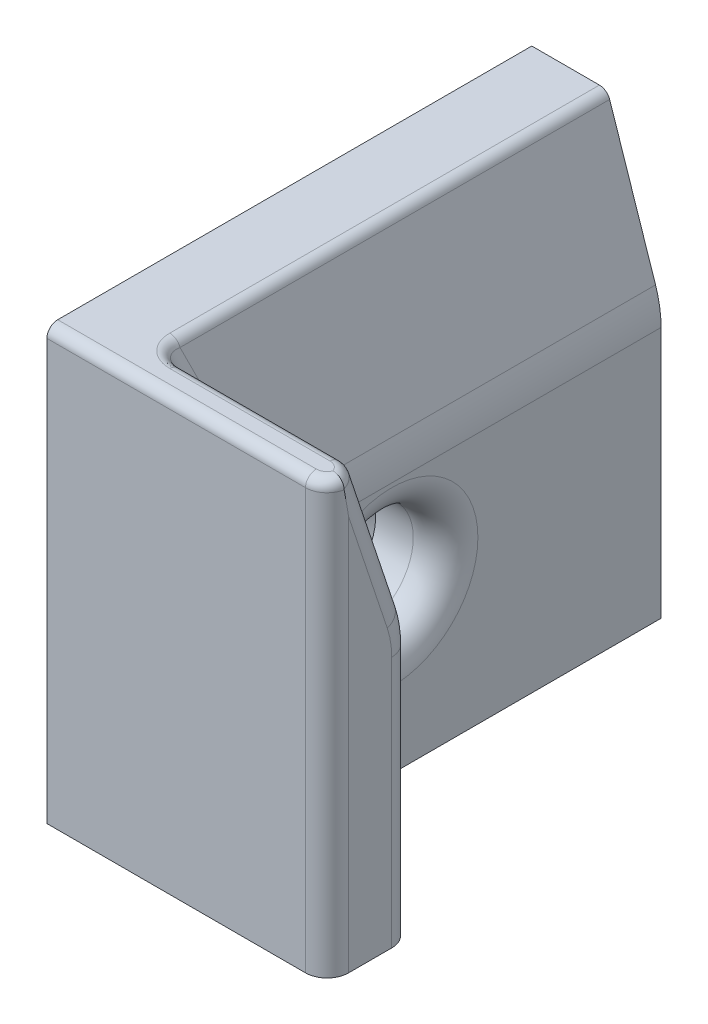
SolidWorks part; units mm, degrees
material "ABS"
ref_plane "Front" through (0, 0, 0) normal (0, 0, 1) x (1, 0, 0)
ref_plane "Top" through (0, 0, 0) normal (0, 1, 0) x (1, 0, 0)
ref_plane "Right" through (0, 0, 0) normal (1, 0, 0) x (0, 0, -1)
sketch "Esquisse1" plane through (0, 0, 0) normal (0, 1, 0) x (1, 0, 0)
  line L0 (-6, 0) -> (6, 0)
  line L1 (6, 0) -> (6, -37)
  line L2 (6, -37) -> (20, -37)
  line L3 (20, -37) -> (20, -45)
  line L4 (20, -45) -> (-6, -45)
  line L7 (-6, -45) -> (-6, 0)
  dimension "D2" = 12
  dimension "D4" = 8
  dimension "D5" = 37
  dimension "D6" = 14
extrude "Boss.-Extru.1" add sketch "Esquisse1" along normal blind 25 and the other way blind 15 from offset 0
chamfer "Chanfrein1" distance 15 distance2 5 2 edges at (13, 25, 37) (6, 25, 18.5) first distance on face at (13, 5, 37) first distance on face at (6, 5, 18.5)
fillet "Congé1" radius 10 2 edges at (13, 10, 37) (6, 10, 18.5)
fillet "Congé2" radius 2 7 edges at (3.2434, 18.2698, 39.7566) (5.8709, 9.979, 37.1291) (20, 18.2698, 39.7566) (20, 9.979, 37.1291) (20, 5, 45) (6, -3.3114, 37) (20, -3.3114, 37)
fillet "Congé3" radius 1 6 edges at (6, 25, 45) (19.2085, 25, 44.5936) (19.2085, 25, 42.4284) (10.4487, 25, 42) (1.5447, 25, 41.4553) (1, 25, 20.0513)
sketch "Esquisse2" plane through (0, 0, 0) normal (0, 1, 0) x (1, 0, 0)
  line L0 (-6, 0) -> (-6, -44) construction
  line L1 (-6, -25) -> (6, -25)
  line L2 (-6, -25) -> (-6, -27)
  line L3 (-0.4827, -30) -> (6, -30)
  line L4 (6, -25) -> (6, -30)
  line L5 (6, 0) -> (6, -35) construction
  line L6 (6, -25) -> (11, -25) construction
  line L9 (-6, -27) -> (-3, -27)
  line L10 (-0.4827, -30) -> (-3, -27)
  line L11 (0.2792, 0) -> (-6, 0) construction
  dimension "D1" = 4
  dimension "D2" = 10
  dimension "D3" = 3
  dimension "D4" = 50
  dimension "D5" = 25
revolve "Enlèvement de matière-Révolution1" cut sketch "Esquisse2" angle 360 about L6
fillet "Congé4" radius 3 1 edges at (6, 0, 30)
